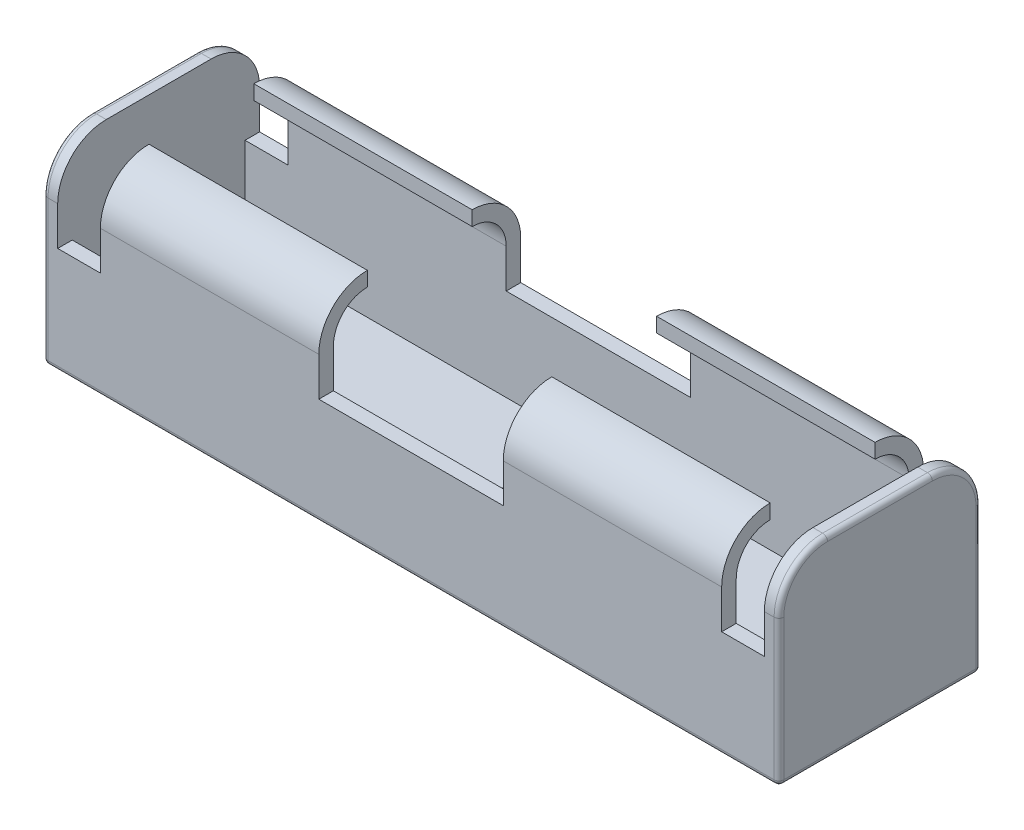
SolidWorks part; units mm, degrees
ref_plane "Alzado" through (0, 0, 0) normal (0, 0, 1) x (1, 0, 0)
ref_plane "Planta" through (0, 0, 0) normal (0, 1, 0) x (1, 0, 0)
ref_plane "Vista lateral" through (0, 0, 0) normal (1, 0, 0) x (0, 0, -1)
sketch "Croquis1" plane through (0, 0, 0) normal (0, 1, 0) x (1, 0, 0)
  line L1 (-37.9, 10.4) -> (37.9, 10.4)
  line L2 (-37.9, 10.4) -> (-37.9, -10.4)
  line L3 (-37.9, -10.4) -> (37.9, -10.4)
  line L4 (37.9, 10.4) -> (37.9, -10.4)
  line L5 (-37.9, 10.4) -> (37.9, -10.4) construction
  line L6 (-37.9, -10.4) -> (37.9, 10.4) construction
  point P0 (0, 0)
  dimension "D1" = 20.8
  dimension "D2" = 75.8
extrude "Saliente-Extruir1" add sketch "Croquis1" along normal blind 20
fillet "Redondeo1" radius 5 2 edges at (0, 20, -10.4) (0, 20, 10.4)
fillet "Redondeo2" radius 0.5 14 edges at (-37.9, 7.5, 10.4) (-37.9, 18.5355, 8.9355) (-37.9, 20, 0) (-37.9, 18.5355, -8.9355) (37.9, 7.5, -10.4) (37.9, 18.5355, -8.9355) (37.9, 20, 0) (37.9, 18.5355, 8.9355) (-37.9, 7.5, -10.4) (-37.9, 0, 0) (37.9, 0, 0) (0, 0, -10.4) (37.9, 7.5, 10.4) (0, 0, 10.4)
shell "Vaciado1" thickness 1.5 removed face at (0, 20, 0)
sketch "Croquis2" plane through (0, 0, 0) normal (0, 0, 1) x (1, 0, 0)
  line L0 (0, 0) -> (0, 20) construction
  line L1 (-36.4, 20) -> (36.4, 20) construction
  line L2 (-9.5, 11) -> (9.5, 11)
  line L3 (9.5, 11) -> (9.5, 20)
  line L4 (9.5, 20) -> (32, 20)
  line L5 (32, 20) -> (32, 11)
  line L6 (32, 11) -> (36.4, 11)
  line L7 (36.4, 11) -> (36.4, 23)
  line L8 (36.4, 23) -> (-36.4, 23)
  line L9 (-36.4, 11) -> (-36.4, 23)
  line L10 (-32, 11) -> (-36.4, 11)
  line L11 (-32, 20) -> (-32, 11)
  line L12 (-9.5, 20) -> (-32, 20)
  line L13 (-9.5, 11) -> (-9.5, 20)
  line L14 (37.9, 15) -> (37.9, 0.5) construction
  point P13 (0, 0)
  point P15 (0, 23)
  point P20 (0, 11)
  dimension "D1" = 19
  dimension "D2" = 22.5
  dimension "D3" = 1.5
  dimension "D4" = 11
  dimension "D5" = 12
extrude "Cortar-Extruir1" cut sketch "Croquis2" against normal through all both and the other way through all
sketch "Croquis3" plane through (0, 1.5, 0) normal (0, 1, 0) x (1, 0, 0)
  circle A0 centre (0, 0) radius 1.75
  dimension "D1" = 3.5
extrude "Cortar-Extruir2" cut sketch "Croquis3" against normal up to next and the other way through all
